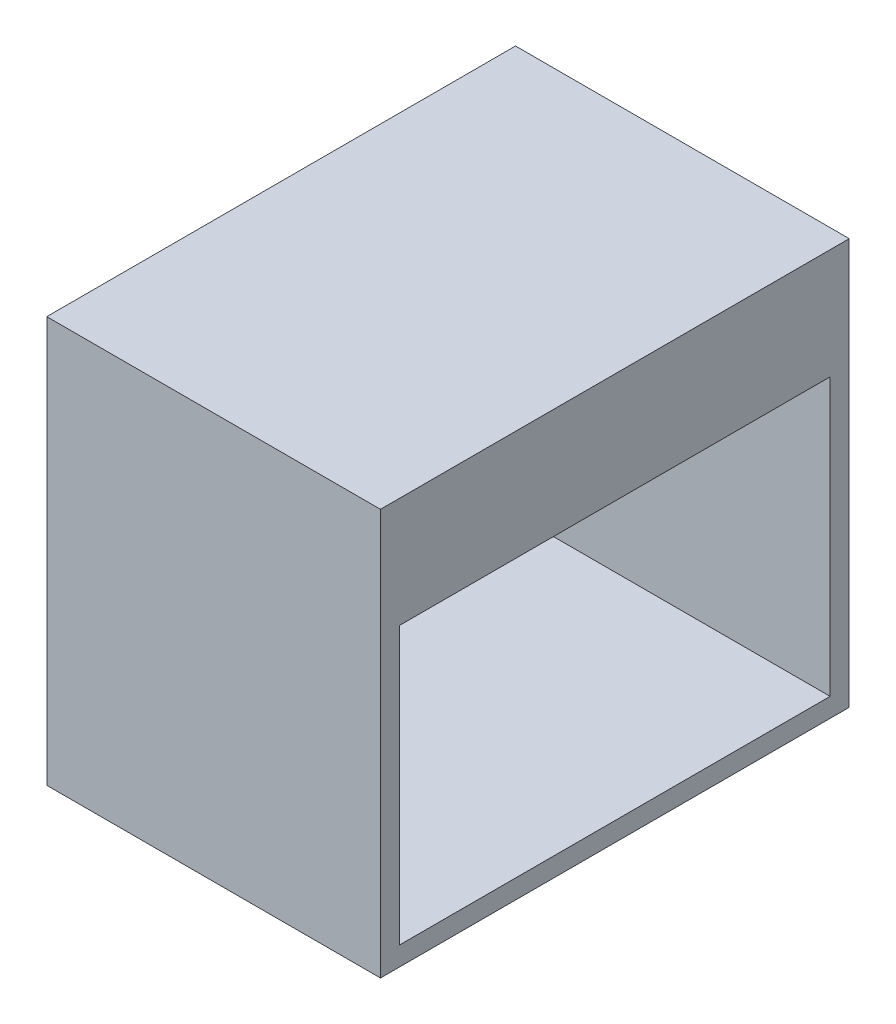
SolidWorks part; units mm, degrees
ref_plane "Front Plane" through (0, 0, 0) normal (0, 0, 1) x (1, 0, 0)
ref_plane "Top Plane" through (0, 0, 0) normal (0, 1, 0) x (1, 0, 0)
ref_plane "Right Plane" through (0, 0, 0) normal (1, 0, 0) x (0, 0, -1)
sketch "Sketch1" plane through (0, 0, 0) normal (0, 1, 0) x (1, 0, 0)
  line L0 (0, 0) -> (370.946, 0)
  line L1 (0, 0) -> (0, 521.0796)
  line L2 (370.946, 0) -> (370.946, 521.0796)
  line L3 (0, 521.0796) -> (370.946, 521.0796)
  dimension "D1" = 521.0796
  dimension "D2" = 370.946
extrude "Boss-Extrude1" add sketch "Sketch1" along normal blind 0.6096
sketch "Sketch3" plane through (0, 0.6096, 0) normal (0, 1, 0) x (1, 0, 0)
  line L0 (0, 521.0796) -> (0, 0) construction
  line L1 (0, 521.0796) -> (0, 0)
  line L2 (0.6096, 521.0796) -> (0.6096, 0)
  line L3 (0, 0) -> (370.946, 0) construction
  line L4 (0, 0) -> (0.6096, 0)
  line L5 (370.946, 521.0796) -> (0, 521.0796) construction
  line L6 (0.6096, 521.0796) -> (0, 521.0796)
  dimension "D1" = 0.6096
extrude "Boss-Extrude2" add sketch "Sketch3" along normal blind 450
sketch "Sketch4" plane through (0, 0.6096, 0) normal (0, 1, 0) x (1, 0, 0)
  line L0 (0.6096, 0) -> (370.946, 0) construction
  line L1 (0.6096, 0) -> (370.946, 0)
  line L2 (0.6096, 0.6096) -> (370.946, 0.6096)
  line L3 (370.946, 0) -> (370.946, 521.0796) construction
  line L4 (370.946, 0) -> (370.946, 0.6096)
  line L5 (0.6096, 0) -> (0.6096, 521.0796) construction
  line L6 (0.6096, 0) -> (0.6096, 0.6096)
  dimension "D1" = 0.6096
extrude "Boss-Extrude3" add sketch "Sketch4" along normal blind 450
sketch "Sketch6" plane through (0, 0.6096, 0) normal (0, 1, 0) x (1, 0, 0)
  line L1 (370.946, 0.6096) -> (370.3364, 0.6096)
  line L2 (370.946, 0.6096) -> (370.946, 520.47)
  line L3 (370.946, 520.47) -> (370.3364, 520.47)
  line L4 (370.3364, 0.6096) -> (370.3364, 520.47)
  dimension "D1" = 0.6096
  dimension "D2" = 519.8604
extrude "Boss-Extrude4" add sketch "Sketch6" along normal blind 20
sketch "Sketch8" plane through (0, 0.6096, 0) normal (0, 1, 0) x (1, 0, 0)
  line L1 (0.6096, 521.0796) -> (370.946, 521.0796)
  line L2 (0.6096, 521.0796) -> (0.6096, 520.47)
  line L3 (0.6096, 520.47) -> (370.946, 520.47)
  line L4 (370.946, 521.0796) -> (370.946, 520.47)
  line L5 (370.946, 520.47) -> (370.946, 521.0796) construction
  dimension "D1" = 0.6096
extrude "Boss-Extrude5" add sketch "Sketch8" along normal up to surface (450 mm away) up to face at (123.8519, 450.6096, -173.8964)
sketch "Sketch9" plane through (0, 450.6096, 0) normal (0, 1, 0) x (1, 0, 0)
  line L1 (0, 0) -> (370.946, 0)
  line L2 (0, 0) -> (0, 521.0796)
  line L3 (0, 521.0796) -> (370.946, 521.0796)
  line L4 (370.946, 0) -> (370.946, 521.0796)
extrude "Boss-Extrude6" add sketch "Sketch9" along normal blind 0.6096
sketch "Sketch11" plane through (0, 450.6096, 0) normal (0, -1, 0) x (1, 0, 0)
  line L0 (0.6096, -520.47) -> (370.946, -520.47) construction
  line L1 (370.946, -0.6096) -> (370.3364, -0.6096)
  line L2 (370.946, -0.6096) -> (370.946, -520.47)
  line L3 (370.946, -520.47) -> (370.3364, -520.47)
  line L4 (370.3364, -0.6096) -> (370.3364, -520.47)
  dimension "D1" = 0.6096
extrude "Boss-Extrude7" add sketch "Sketch11" along normal blind 121.174
sketch "Sketch10" plane through (0, 20.6096, 0) normal (0, 1, 0) x (1, 0, 0)
  line L0 (370.946, 0.6096) -> (370.946, 520.47) construction
  line L1 (370.3364, 0.6096) -> (370.946, 0.6096)
  line L2 (370.3364, 0.6096) -> (370.3364, 20.6096)
  line L3 (370.3364, 20.6096) -> (370.946, 20.6096)
  line L4 (370.946, 0.6096) -> (370.946, 20.6096)
  line L5 (370.3364, 520.47) -> (370.3364, 0.6096) construction
  line L6 (370.946, 520.47) -> (370.3364, 520.47)
  line L7 (370.946, 520.47) -> (370.946, 500.47)
  line L8 (370.946, 500.47) -> (370.3364, 500.47)
  line L9 (370.3364, 520.47) -> (370.3364, 500.47)
  dimension "D1" = 20
  dimension "D2" = 20
extrude "Boss-Extrude8" add sketch "Sketch10" along normal up to surface (308.826 mm away) up to face at (370.6412, 329.4356, -260.5398)
sketch "Sketch13" plane through (370.946, 0, 0) normal (1, 0, 0) x (0, 0, -1)
  line L0 (500.47, 329.4356) -> (500.47, 20.6096) construction
  line L1 (20.6096, 20.6096) -> (500.47, 20.6096)
  line L2 (20.6096, 20.6096) -> (20.6096, 21.2192)
  line L3 (20.6096, 21.2192) -> (500.47, 21.2192)
  line L4 (500.47, 20.6096) -> (500.47, 21.2192)
  dimension "D1" = 0.6096
extrude "Boss-Extrude9" add sketch "Sketch13" against normal blind 350.34
sketch "Sketch14" plane through (0, 21.2192, 0) normal (0, 1, 0) x (1, 0, 0)
  line L0 (20.606, 500.47) -> (370.3364, 500.47) construction
  line L1 (20.606, 20.6096) -> (21.2156, 20.6096)
  line L2 (20.606, 20.6096) -> (20.606, 500.47)
  line L3 (20.606, 500.47) -> (21.2156, 500.47)
  line L4 (21.2156, 20.6096) -> (21.2156, 500.47)
  dimension "D1" = 0.6096
extrude "Boss-Extrude10" add sketch "Sketch14" along normal up to surface (429.3904 mm away) up to face at (185.473, 450.6096, -260.5398)
sketch "Sketch15" plane through (0, 21.2192, 0) normal (0, 1, 0) x (1, 0, 0)
  line L0 (370.946, 500.47) -> (370.946, 20.6096) construction
  line L1 (21.2156, 20.6096) -> (370.946, 20.6096)
  line L2 (21.2156, 20.6096) -> (21.2156, 21.2192)
  line L3 (21.2156, 21.2192) -> (370.946, 21.2192)
  line L4 (370.946, 20.6096) -> (370.946, 21.2192)
  line L6 (21.2156, 500.47) -> (370.946, 500.47)
  line L7 (21.2156, 500.47) -> (21.2156, 499.8604)
  line L8 (21.2156, 499.8604) -> (370.946, 499.8604)
  line L9 (370.946, 500.47) -> (370.946, 499.8604)
  dimension "D1" = 0.6096
  dimension "D2" = 0.6096
extrude "Boss-Extrude11" add sketch "Sketch15" along normal up to surface (429.3904 mm away) up to face at (185.473, 450.6096, -260.5398)
sketch "Sketch17" plane through (370.946, 0, 0) normal (1, 0, 0) x (0, 0, -1)
  line L0 (499.8604, 329.4356) -> (499.8604, 21.2192) construction
  line L1 (21.2192, 329.4356) -> (499.8604, 329.4356)
  line L2 (21.2192, 329.4356) -> (21.2192, 328.826)
  line L3 (21.2192, 328.826) -> (499.8604, 328.826)
  line L4 (499.8604, 329.4356) -> (499.8604, 328.826)
  dimension "D1" = 0.6096
extrude "Boss-Extrude12" add sketch "Sketch17" against normal blind 20
